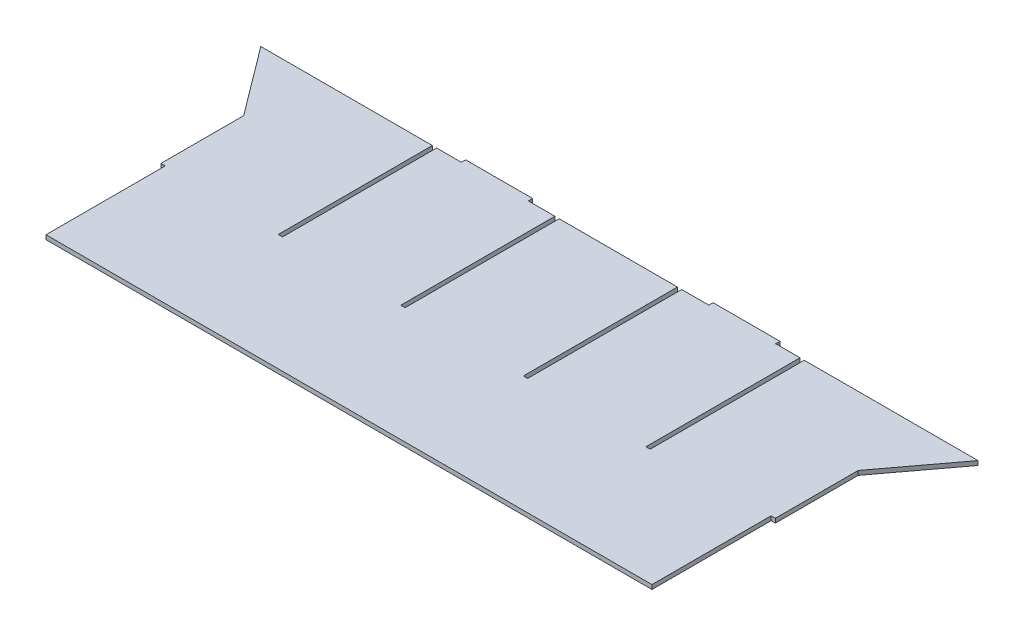
SolidWorks part; units mm, degrees
material "Custom Plastic"
ref_plane "X-Y Datum" through (0, 0, 0) normal (0, 0, 1) x (1, 0, 0)
ref_plane "X-Z Datum" through (0, 0, 0) normal (0, 1, 0) x (1, 0, 0)
ref_plane "Y-Z Datum" through (0, 0, 0) normal (1, 0, 0) x (0, 0, -1)
sketch "Sketch1" plane through (0, 0, 0) normal (0, 0, 1) x (1, 0, 0)
  line L1 (-227.966, -1.5875) -> (227.966, -1.5875)
  line L2 (-227.966, -1.5875) -> (-227.966, 1.5875)
  line L3 (-227.966, 1.5875) -> (227.966, 1.5875)
  line L4 (227.966, -1.5875) -> (227.966, 1.5875)
  line L5 (-227.966, -1.5875) -> (227.966, 1.5875) construction
  line L6 (-227.966, 1.5875) -> (227.966, -1.5875) construction
  point P0 (0, 0)
  dimension "D1" = 3.175
  dimension "D2" = 455.932
extrude "Boss-Extrude1" add sketch "Sketch1" along normal blind 200.642
sketch "Sketch2" plane through (0, 1.5875, 0) normal (0, 1, 0) x (1, 0, 0)
  line L0 (227.966, 0) -> (224.791, 0)
  line L1 (227.966, 0) -> (-227.966, 0) construction
  line L2 (224.791, 0) -> (137.161, 0)
  line L3 (137.161, 0) -> (133.986, 0)
  line L10 (133.986, 0) -> (137.161, 0)
  line L11 (133.986, 0) -> (133.986, -114.3)
  line L12 (133.986, -114.3) -> (137.161, -114.3)
  line L13 (137.161, 0) -> (137.161, -114.3)
  line M2 (227.966, 0) -> (-227.966, 0)
  dimension "D1" = 87.63
  dimension "D2" = 3.175
  dimension "D3" = 114.3
extrude "Cut-Extrude1" cut sketch "Sketch2" against normal through all contours L13 L11 L12 M2 region at (135.5735, 1.5875, 57.15)
pattern_linear "LPattern1" count 4 spacing 90.932 along (-1, 0, 0) of "Cut-Extrude1"
sketch "Sketch3" plane through (0, 0, 0) normal (0, 0, -1) x (-1, 0, 0)
  line L1 (-115.966, 1.5875) -> (-66.3072, 1.5875)
  line L2 (-115.966, 1.5875) -> (-115.966, -1.5875)
  line L3 (-115.966, -1.5875) -> (-66.3072, -1.5875)
  line L4 (-66.3072, 1.5875) -> (-66.3072, -1.5875)
  line L5 (67.5982, 1.5875) -> (117.257, 1.5875)
  line L6 (67.5982, 1.5875) -> (67.5982, -1.5875)
  line L7 (67.5982, -1.5875) -> (117.257, -1.5875)
  line L8 (117.257, 1.5875) -> (117.257, -1.5875)
extrude "Boss-Extrude2" add sketch "Sketch3" along normal blind 3.175
sketch "Sketch4" plane through (0, -1.5875, 0) normal (0, -1, 0) x (1, 0, 0)
  line L0 (-227.966, 0) -> (-266.066, 0)
  line L1 (-266.066, 0) -> (-227.966, 50.8)
  line L2 (-227.966, 200.642) -> (-227.966, 0) construction
  line L3 (-227.966, 50.8) -> (-227.966, 0)
  dimension "D1" = 38.1
  dimension "D2" = 50.8
extrude "Boss-Extrude3" add sketch "Sketch4" against normal blind 3.175
mirror "Mirror1" about plane through (0, 0, 0) normal (1, 0, 0) of "Boss-Extrude3"
sketch "Sketch5" plane through (0, -1.5875, 0) normal (0, -1, 0) x (1, 0, 0)
  line L1 (-227.966, 200.642) -> (-224.791, 200.642)
  line L2 (-227.966, 200.642) -> (-227.966, 112.25)
  line L3 (-227.966, 112.25) -> (-224.791, 112.25)
  line L4 (-224.791, 200.642) -> (-224.791, 112.25)
  dimension "D1" = 3.175
  dimension "D2" = 88.392
extrude "Cut-Extrude2" cut sketch "Sketch5" against normal blind 3.175
mirror "Mirror2" about plane through (0, 0, 0) normal (1, 0, 0) of "Cut-Extrude2"
